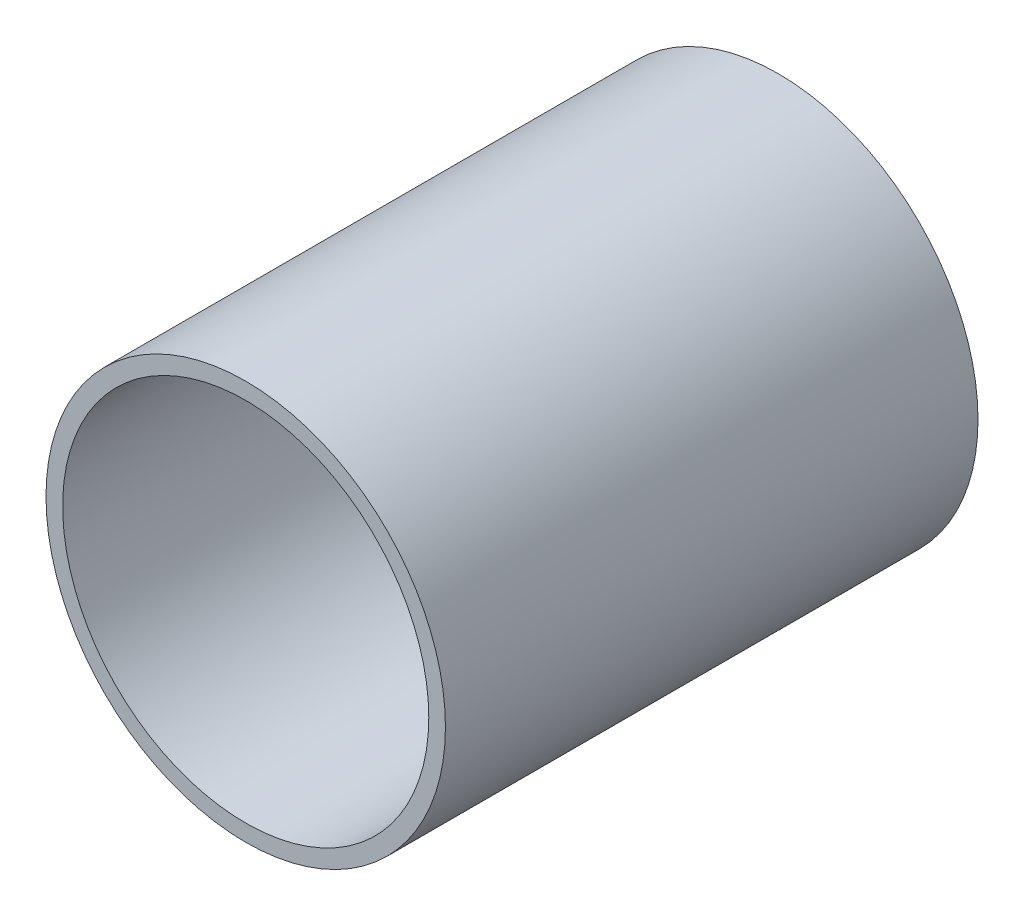
SolidWorks part; units mm, degrees
ref_plane "Front Plane" through (0, 0, 0) normal (0, 0, 1) x (1, 0, 0)
ref_plane "Top Plane" through (0, 0, 0) normal (0, 1, 0) x (1, 0, 0)
ref_plane "Right Plane" through (0, 0, 0) normal (1, 0, 0) x (0, 0, -1)
sketch "Sketch1" plane through (0, 0, 0) normal (0, 0, 1) x (1, 0, 0)
  circle A0 centre (0, 0) radius 34.925
  circle A1 centre (0, 0) radius 38.1
extrude "Boss-Extrude1" add sketch "Sketch1" along normal blind 101.6
